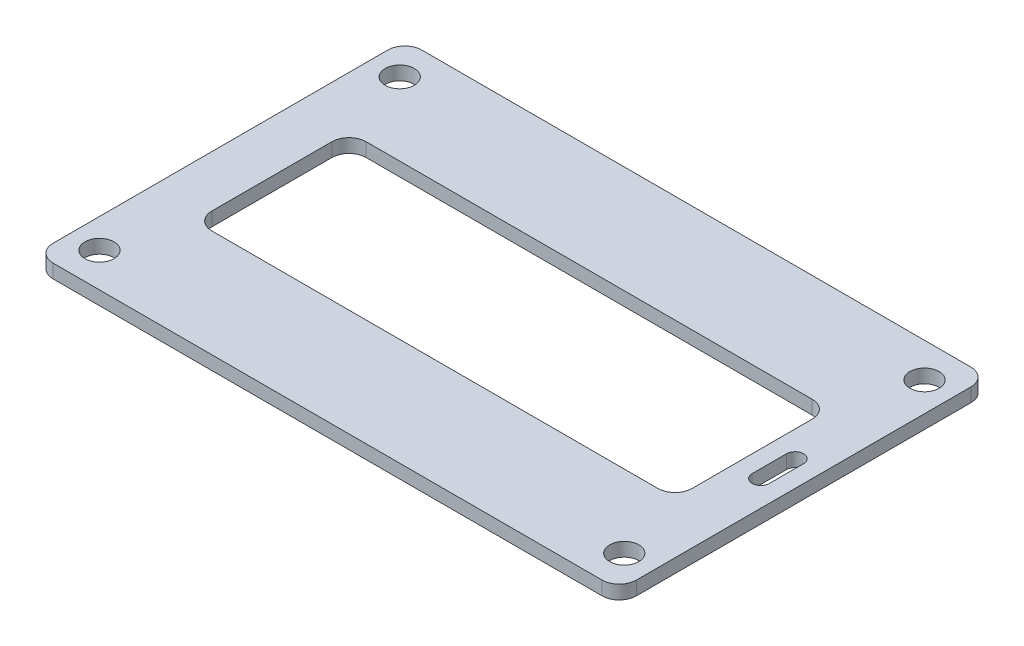
SolidWorks part; units mm, degrees
material "EPDM"
ref_plane "Front Plane" through (0, 0, 0) normal (0, 0, 1) x (1, 0, 0)
ref_plane "Top Plane" through (0, 0, 0) normal (0, 1, 0) x (1, 0, 0)
ref_plane "Right Plane" through (0, 0, 0) normal (1, 0, 0) x (0, 0, -1)
sketch "Sketch1" plane through (0, 0, 0) normal (0, 1, 0) x (1, 0, 0)
  line L0 (-32, -21.5) -> (32, -21.5) construction
  line L1 (-34, 19.5) -> (-34, -19.5) construction
  line L2 (32, 21.5) -> (-32, 21.5) construction
  line L3 (34, -19.5) -> (34, 19.5) construction
  line L4 (28, -7) -> (28, 7) construction
  line L5 (-26, -9) -> (26, -9) construction
  line L6 (-28, 7) -> (-28, -7) construction
  line L7 (26, 9) -> (-26, 9) construction
  line L8 (-32, -21.5) -> (32, -21.5)
  line L9 (-34, 19.5) -> (-34, -19.5)
  line L10 (32, 21.5) -> (-32, 21.5)
  line L11 (34, -19.5) -> (34, 19.5)
  line L12 (28, -7) -> (28, 7)
  line L13 (-26, -9) -> (26, -9)
  line L14 (-28, 7) -> (-28, -7)
  line L15 (26, 9) -> (-26, 9)
  line L16 (30, 2) -> (30, -2) construction
  line L17 (30, 2) -> (30, -2)
  line L18 (32, -2) -> (32, 2) construction
  line L19 (32, -2) -> (32, 2)
  circle A1 centre (30.5885, 17.5) radius 1.7 construction
  circle A2 centre (-30.5885, 17.5) radius 1.7 construction
  circle A3 centre (-30.5885, -17.5) radius 1.7 construction
  circle A4 centre (30.5885, -17.5) radius 1.7 construction
  arc A5 (32, -21.5) -> (34, -19.5) centre (32, -19.5) ccw construction
  arc A6 (-34, -19.5) -> (-32, -21.5) centre (-32, -19.5) ccw construction
  arc A7 (-32, 21.5) -> (-34, 19.5) centre (-32, 19.5) ccw construction
  arc A8 (34, 19.5) -> (32, 21.5) centre (32, 19.5) ccw construction
  arc A9 (28, 7) -> (26, 9) centre (26, 7) ccw construction
  arc A10 (26, -9) -> (28, -7) centre (26, -7) ccw construction
  arc A11 (-28, -7) -> (-26, -9) centre (-26, -7) ccw construction
  arc A12 (-26, 9) -> (-28, 7) centre (-26, 7) ccw construction
  circle A14 centre (30.5885, 17.5) radius 1.7
  circle A15 centre (-30.5885, 17.5) radius 1.7
  circle A16 centre (-30.5885, -17.5) radius 1.7
  circle A17 centre (30.5885, -17.5) radius 1.7
  arc A18 (32, -21.5) -> (34, -19.5) centre (32, -19.5) ccw
  arc A19 (-34, -19.5) -> (-32, -21.5) centre (-32, -19.5) ccw
  arc A20 (-32, 21.5) -> (-34, 19.5) centre (-32, 19.5) ccw
  arc A21 (34, 19.5) -> (32, 21.5) centre (32, 19.5) ccw
  arc A22 (28, 7) -> (26, 9) centre (26, 7) ccw
  arc A23 (26, -9) -> (28, -7) centre (26, -7) ccw
  arc A24 (-28, -7) -> (-26, -9) centre (-26, -7) ccw
  arc A25 (-26, 9) -> (-28, 7) centre (-26, 7) ccw
  arc A26 (32, 2) -> (30, 2) centre (31, 2) ccw construction
  arc A27 (32, 2) -> (30, 2) centre (31, 2) ccw
  arc A28 (30, -2) -> (32, -2) centre (31, -2) ccw construction
  arc A29 (30, -2) -> (32, -2) centre (31, -2) ccw
extrude "Boss-Extrude1" add sketch "Sketch1" along normal blind 1.6
